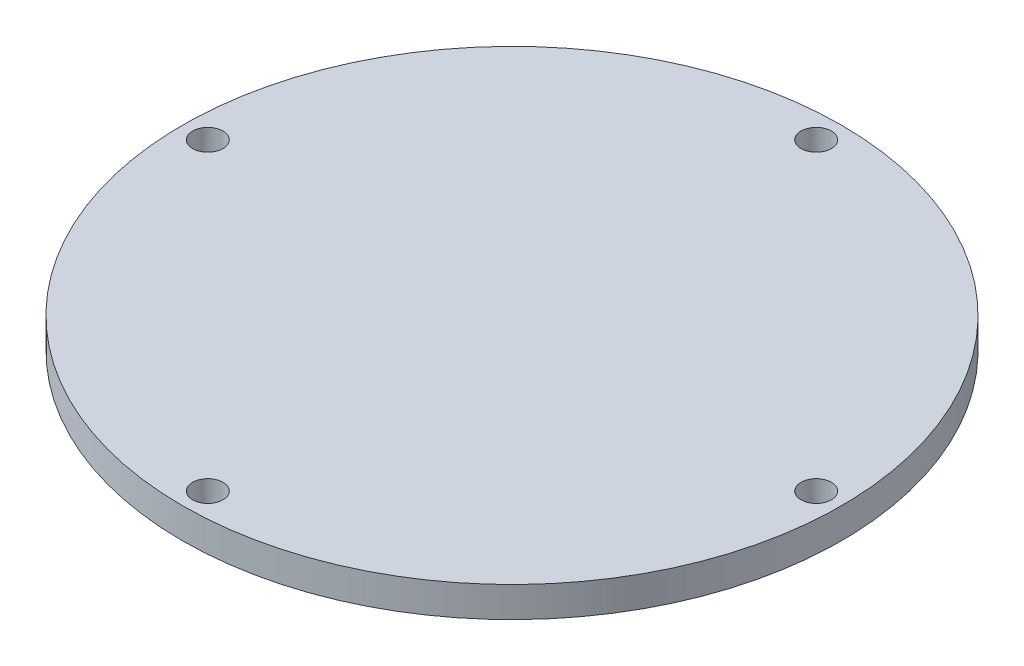
SolidWorks part; units mm, degrees
ref_plane "Front Plane" through (0, 0, 0) normal (0, 0, 1) x (1, 0, 0)
ref_plane "Top Plane" through (0, 0, 0) normal (0, 1, 0) x (1, 0, 0)
ref_plane "Right Plane" through (0, 0, 0) normal (1, 0, 0) x (0, 0, -1)
sketch "Sketch1" plane through (0, 0, 0) normal (0, 1, 0) x (1, 0, 0)
  circle A0 centre (0, 0) radius 32.5
  circle A1 centre (-30, 0) radius 1.5
  circle A2 centre (0, 0) radius 30 construction
  circle A3 centre (0, 30) radius 1.5
  circle A4 centre (30, 0) radius 1.5
  circle A5 centre (0, -30) radius 1.5
  point P15 (0, 0)
  dimension "D1" = 65
  dimension "D2" = 2.5
  dimension "D3" = 3
  dimension "D4" = 4
extrude "Boss-Extrude1" add sketch "Sketch1" along normal blind 3
